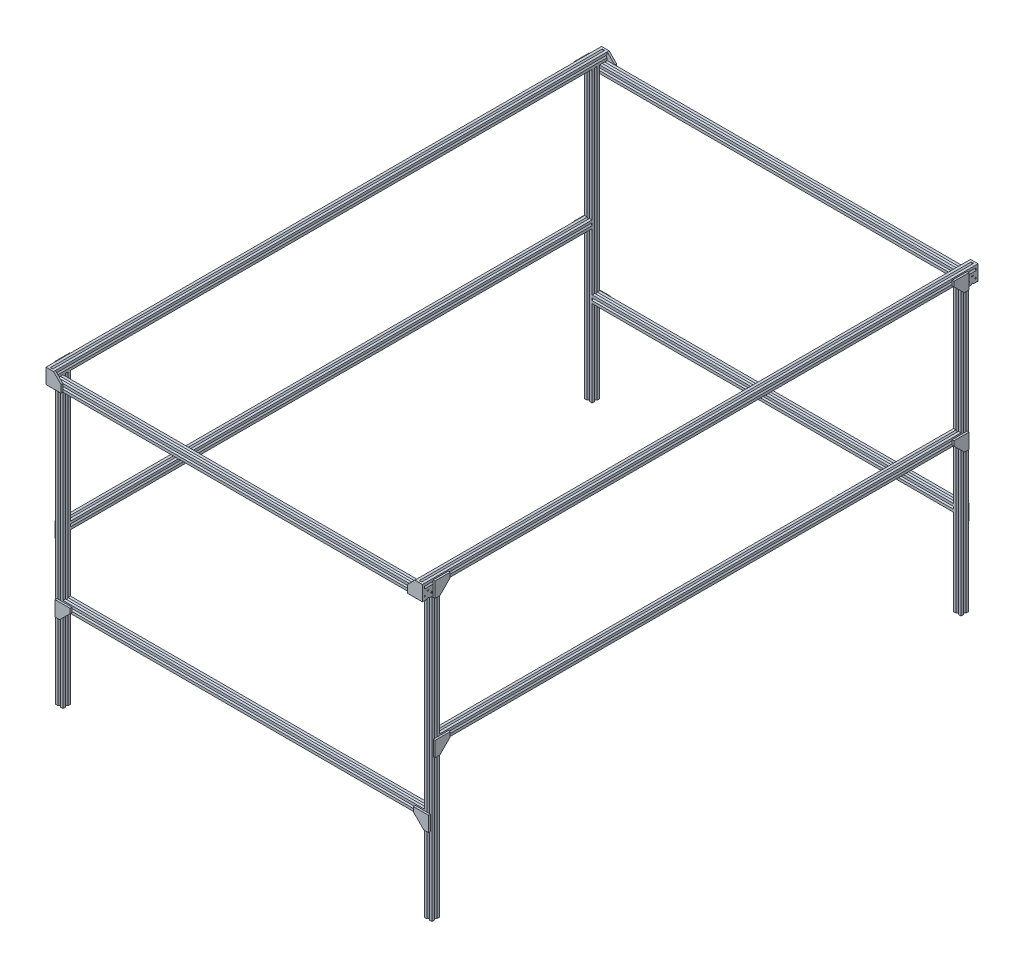
SolidWorks part; units mm, degrees
ref_plane "Front Plane" through (0, 0, 0) normal (0, 0, 1) x (1, 0, 0)
ref_plane "Top Plane" through (0, 0, 0) normal (0, 1, 0) x (1, 0, 0)
ref_plane "Right Plane" through (0, 0, 0) normal (1, 0, 0) x (0, 0, -1)
sketch "Sketch1" plane through (0, 0, 0) normal (0, 1, 0) x (1, 0, 0)
  line L48 (-13.2, 20) -> (-10, 16.8)
  line L49 (-10, 16.8) -> (-6.8, 20)
  line L50 (0, 13.2) -> (-3.2, 10)
  line L51 (-3.2, 10) -> (0, 6.8)
  line L100 (0, 0) -> (-28.059, 28.059) construction
  line L101 (-20, 0) -> (-13.2, 0)
  line L102 (-20, 0) -> (-20, 6.8)
  line L103 (-20, 20) -> (-13.2, 20)
  line L104 (0, 0) -> (0, 6.8)
  line L105 (-13.2, 20) -> (-13.2, 18.2)
  line L106 (0, 20) -> (-11.7678, 8.2322) construction
  line L107 (-7.05, 6.1) -> (-12.95, 6.1)
  line L108 (-6.1, 7.05) -> (-6.1, 12.95)
  line L109 (-7.05, 13.9) -> (-12.95, 13.9)
  line L110 (-13.9, 7.05) -> (-13.9, 12.95)
  line L111 (-6.1, 6.1) -> (-13.9, 13.9) construction
  line L112 (-6.1, 13.9) -> (-13.9, 6.1) construction
  line L113 (-15.45, 16.4) -> (-12.95, 13.9)
  line L114 (-6.8, 18.2) -> (-6.8, 20)
  line L115 (-18.2, 6.8) -> (-20, 6.8)
  line L116 (-20, 13.2) -> (-20, 20)
  line L117 (-20, 13.2) -> (-18.2, 13.2)
  line L118 (-10, 10) -> (-10, 13.9) construction
  line L119 (-3.6, 4.55) -> (-6.1, 7.05)
  line L120 (-15.45, 16.4) -> (-15.45, 18.2)
  line L121 (-15.45, 18.2) -> (-13.2, 18.2)
  line L122 (-6.8, 18.2) -> (-4.55, 18.2)
  line L123 (-4.55, 18.2) -> (-4.55, 16.4)
  line L124 (-4.55, 16.4) -> (-7.05, 13.9)
  line L125 (-3.6, 4.55) -> (-1.8, 4.55)
  line L126 (-1.8, 4.55) -> (-1.8, 6.8)
  line L127 (0, 6.8) -> (-1.8, 6.8)
  line L128 (-1.8, 13.2) -> (0, 13.2)
  line L129 (-1.8, 13.2) -> (-1.8, 15.45)
  line L130 (-1.8, 15.45) -> (-3.6, 15.45)
  line L131 (-3.6, 15.45) -> (-6.1, 12.95)
  line L132 (-18.2, 4.55) -> (-16.4, 4.55)
  line L133 (-16.4, 15.45) -> (-13.9, 12.95)
  line L134 (-16.4, 15.45) -> (-18.2, 15.45)
  line L135 (-18.2, 15.45) -> (-18.2, 13.2)
  line L136 (-20, 13.2) -> (-18.2, 13.2)
  line L137 (-18.2, 6.8) -> (-20, 6.8)
  line L138 (-16.4, 4.55) -> (-13.9, 7.05)
  line L139 (-18.2, 6.8) -> (-18.2, 4.55)
  line L140 (-4.55, 3.6) -> (-7.05, 6.1)
  line L141 (-15.45, 3.6) -> (-12.95, 6.1)
  line L142 (-15.45, 1.8) -> (-15.45, 3.6)
  line L143 (-13.2, 1.8) -> (-15.45, 1.8)
  line L144 (-13.2, 1.8) -> (-13.2, 0)
  line L145 (-4.55, 3.6) -> (-4.55, 1.8)
  line L146 (-4.55, 1.8) -> (-6.8, 1.8)
  line L147 (-6.8, 0) -> (-6.8, 1.8)
  line L148 (-6.8, 20) -> (0, 20)
  line L149 (0, 13.2) -> (0, 20)
  line L150 (-6.8, 0) -> (0, 0)
  line L151 (-13.9, 6.1) -> (-25.5045, -5.5045) construction
  line L152 (-6.8, 0) -> (-10, 3.2)
  line L153 (-10, 3.2) -> (-13.2, 0)
  line L154 (-20, 6.8) -> (-16.8, 10)
  line L155 (-16.8, 10) -> (-20, 13.2)
  circle A1 centre (-10, 10) radius 2.5
  point P140 (-10, 16.4)
  point P154 (-6.8, 19.1)
  point P161 (-19.1, 6.8)
  dimension "D13" = 5
  dimension "D12" = 20
  dimension "D14" = 7.8
  dimension "D15" = 7.8
  dimension "D16" = 6.8
  dimension "D17" = 6.8
  dimension "D18" = 1.8
  dimension "D19" = 10.9
  dimension "D20" = 1.8
  dimension "D21" = 10.9
  dimension "D22" = 20
extrude "Vertical Leg" add sketch "Sketch1" along normal blind 767.075 contours L147 L150 L104 L127 L126 L125 L119 L108 L131 L130 L129 L128 L149 L148 L114 L122 L123 L124 L109 L113 L120 L121 L105 L103 L116 L117 L135 L134 L133 L110 L138 L132 L139 L115 L102 L101 L144 L143 L142 L141 L107 L140 L145 L146 A1 | L124 L123 L122 L114 L49 L48 L105 L121 L120 L113 L109 | L155 L154 L115 L139 L132 L138 L110 L133 L134 L135 L117 | L130 L131 L108 L119 L125 L126 L127 L51 L50 L128 L129 | A1 | L153 L152 L147 L146 L145 L140 L107 L141 L142 L143 L144 region at (-13.4828, 0, -19.1) region at (-10, 0, -16.3803) region at (-16.3803, 0, -10) region at (-3.6197, 0, -10) region at (-10, 0, -3.6197) region at (-10, 0, -10)
sketch "Sketch2" plane through (-20, 0, 0) normal (-1, 0, 0) x (0, 0, 1)
  line L0 (0, 228.6) -> (-28.059, 256.659) construction
  line L1 (-20, 228.6) -> (-13.2, 228.6)
  line L2 (-20, 228.6) -> (-20, 235.4)
  line L3 (-20, 248.6) -> (-13.2, 248.6)
  line L4 (0, 228.6) -> (0, 235.4)
  line L5 (-13.2, 248.6) -> (-13.2, 246.8)
  line L6 (0, 248.6) -> (-11.7678, 236.8322) construction
  line L7 (-7.05, 234.7) -> (-12.95, 234.7)
  line L8 (-6.1, 235.65) -> (-6.1, 241.55)
  line L9 (-7.05, 242.5) -> (-12.95, 242.5)
  line L10 (-13.9, 235.65) -> (-13.9, 241.55)
  line L11 (-6.1, 234.7) -> (-13.9, 242.5) construction
  line L12 (-6.1, 242.5) -> (-13.9, 234.7) construction
  line L13 (-15.45, 245) -> (-12.95, 242.5)
  line L14 (-6.8, 246.8) -> (-6.8, 248.6)
  line L15 (-18.2, 235.4) -> (-20, 235.4)
  line L16 (-20, 241.8) -> (-20, 248.6)
  line L17 (-20, 241.8) -> (-18.2, 241.8)
  line L18 (-10, 238.6) -> (-10, 242.5) construction
  line L19 (-3.6, 233.15) -> (-6.1, 235.65)
  line L20 (-15.45, 245) -> (-15.45, 246.8)
  line L21 (-15.45, 246.8) -> (-13.2, 246.8)
  line L22 (-6.8, 246.8) -> (-4.55, 246.8)
  line L23 (-4.55, 246.8) -> (-4.55, 245)
  line L24 (-4.55, 245) -> (-7.05, 242.5)
  line L25 (-3.6, 233.15) -> (-1.8, 233.15)
  line L26 (-1.8, 233.15) -> (-1.8, 235.4)
  line L27 (0, 235.4) -> (-1.8, 235.4)
  line L28 (-1.8, 241.8) -> (0, 241.8)
  line L29 (-1.8, 241.8) -> (-1.8, 244.05)
  line L30 (-1.8, 244.05) -> (-3.6, 244.05)
  line L31 (-3.6, 244.05) -> (-6.1, 241.55)
  line L32 (-18.2, 233.15) -> (-16.4, 233.15)
  line L33 (-16.4, 244.05) -> (-13.9, 241.55)
  line L34 (-16.4, 244.05) -> (-18.2, 244.05)
  line L35 (-18.2, 244.05) -> (-18.2, 241.8)
  line L36 (-20, 241.8) -> (-18.2, 241.8)
  line L37 (-18.2, 235.4) -> (-20, 235.4)
  line L38 (-16.4, 233.15) -> (-13.9, 235.65)
  line L39 (-18.2, 235.4) -> (-18.2, 233.15)
  line L40 (-4.55, 232.2) -> (-7.05, 234.7)
  line L41 (-15.45, 232.2) -> (-12.95, 234.7)
  line L42 (-15.45, 230.4) -> (-15.45, 232.2)
  line L43 (-13.2, 230.4) -> (-15.45, 230.4)
  line L44 (-13.2, 230.4) -> (-13.2, 228.6)
  line L45 (-4.55, 232.2) -> (-4.55, 230.4)
  line L46 (-4.55, 230.4) -> (-6.8, 230.4)
  line L47 (-6.8, 228.6) -> (-6.8, 230.4)
  line L48 (-6.8, 248.6) -> (0, 248.6)
  line L49 (0, 241.8) -> (0, 248.6)
  line L50 (-6.8, 228.6) -> (0, 228.6)
  line L51 (-13.9, 234.7) -> (-25.5045, 223.0955) construction
  line L52 (-103.3225, 228.6) -> (77.3135, 228.6) construction
  line L53 (0, 0) -> (-6.8, 0) construction
  line L54 (20, 747.075) -> (-8.059, 775.134) construction
  line L55 (0, 747.075) -> (6.8, 747.075)
  line L56 (0, 747.075) -> (0, 753.875)
  line L57 (0, 767.075) -> (6.8, 767.075)
  line L58 (20, 747.075) -> (20, 753.875)
  line L59 (6.8, 767.075) -> (6.8, 765.275)
  line L60 (20, 767.075) -> (8.2322, 755.3072) construction
  line L61 (12.95, 753.175) -> (7.05, 753.175)
  line L62 (13.9, 754.125) -> (13.9, 760.025)
  line L63 (12.95, 760.975) -> (7.05, 760.975)
  line L64 (6.1, 754.125) -> (6.1, 760.025)
  line L65 (13.9, 753.175) -> (6.1, 760.975) construction
  line L66 (13.9, 760.975) -> (6.1, 753.175) construction
  line L67 (4.55, 763.475) -> (7.05, 760.975)
  line L68 (13.2, 765.275) -> (13.2, 767.075)
  line L69 (1.8, 753.875) -> (0, 753.875)
  line L70 (0, 760.275) -> (0, 767.075)
  line L71 (0, 760.275) -> (1.8, 760.275)
  line L72 (10, 757.075) -> (10, 760.975) construction
  line L73 (16.4, 751.625) -> (13.9, 754.125)
  line L74 (4.55, 763.475) -> (4.55, 765.275)
  line L75 (4.55, 765.275) -> (6.8, 765.275)
  line L76 (13.2, 765.275) -> (15.45, 765.275)
  line L77 (15.45, 765.275) -> (15.45, 763.475)
  line L78 (15.45, 763.475) -> (12.95, 760.975)
  line L79 (16.4, 751.625) -> (18.2, 751.625)
  line L80 (18.2, 751.625) -> (18.2, 753.875)
  line L81 (20, 753.875) -> (18.2, 753.875)
  line L82 (18.2, 760.275) -> (20, 760.275)
  line L83 (18.2, 760.275) -> (18.2, 762.525)
  line L84 (18.2, 762.525) -> (16.4, 762.525)
  line L85 (16.4, 762.525) -> (13.9, 760.025)
  line L86 (1.8, 751.625) -> (3.6, 751.625)
  line L87 (3.6, 762.525) -> (6.1, 760.025)
  line L88 (3.6, 762.525) -> (1.8, 762.525)
  line L89 (1.8, 762.525) -> (1.8, 760.275)
  line L90 (0, 760.275) -> (1.8, 760.275)
  line L91 (1.8, 753.875) -> (0, 753.875)
  line L92 (3.6, 751.625) -> (6.1, 754.125)
  line L93 (1.8, 753.875) -> (1.8, 751.625)
  line L94 (15.45, 750.675) -> (12.95, 753.175)
  line L95 (4.55, 750.675) -> (7.05, 753.175)
  line L96 (4.55, 748.875) -> (4.55, 750.675)
  line L97 (6.8, 748.875) -> (4.55, 748.875)
  line L98 (6.8, 748.875) -> (6.8, 747.075)
  line L99 (15.45, 750.675) -> (15.45, 748.875)
  line L100 (15.45, 748.875) -> (13.2, 748.875)
  line L101 (13.2, 747.075) -> (13.2, 748.875)
  line L102 (13.2, 767.075) -> (20, 767.075)
  line L103 (20, 760.275) -> (20, 767.075)
  line L104 (13.2, 747.075) -> (20, 747.075)
  line L105 (6.1, 753.175) -> (-5.5045, 741.5705) construction
  line L106 (-13.2, 248.6) -> (-10, 245.4)
  line L107 (-10, 767.075) -> (-10, 0) construction
  line L108 (-10, 245.4) -> (-6.8, 248.6)
  line L109 (0, 241.8) -> (-3.2, 238.6)
  line L110 (-3.2, 238.6) -> (0, 235.4)
  line L111 (-6.8, 228.6) -> (-10, 231.8)
  line L112 (-10, 231.8) -> (-13.2, 228.6)
  line L113 (-20, 235.4) -> (-16.8, 238.6)
  line L114 (-16.8, 238.6) -> (-20, 241.8)
  line L115 (6.8, 767.075) -> (10, 763.875)
  line L116 (10, 763.875) -> (13.2, 767.075)
  line L117 (20, 760.275) -> (16.8, 757.075)
  line L118 (16.8, 757.075) -> (20, 753.875)
  line L119 (13.2, 747.075) -> (10, 750.275)
  line L120 (10, 750.275) -> (6.8, 747.075)
  line L121 (0, 753.875) -> (3.2, 757.075)
  line L122 (3.2, 757.075) -> (0, 760.275)
  circle A0 centre (-10, 238.6) radius 2.5
  circle A1 centre (10, 757.075) radius 2.5
  point P23 (-10, 245)
  point P44 (-19.1, 235.4)
  point P84 (10, 763.475)
  point P98 (13.2, 766.175)
  point P105 (0.9, 753.875)
  line M5 (-20, 767.075) -> (-20, 0)
  line M114 (-13.2, 0) -> (-13.2, 767.075)
  dimension "D2" = 5
  dimension "D14" = 5
  dimension "D1" = 20
  dimension "D3" = 7.8
  dimension "D4" = 7.8
  dimension "D5" = 6.8
  dimension "D6" = 6.8
  dimension "D7" = 1.8
  dimension "D8" = 10.9
  dimension "D9" = 1.8
  dimension "D10" = 10.9
  dimension "D11" = 20
  dimension "D12" = 228.6
  dimension "D13" = 20
  dimension "D15" = 7.8
  dimension "D16" = 7.8
  dimension "D17" = 6.8
  dimension "D18" = 6.8
  dimension "D19" = 1.8
  dimension "D20" = 10.9
  dimension "D21" = 1.8
  dimension "D22" = 10.9
  dimension "D23" = 20
extrude "Short Horizontal" add sketch "Sketch2" along normal blind 479.425 contours L47 L50 L4 L27 L26 L25 L19 L8 L31 L30 L29 L28 L49 L48 L14 L22 L23 L24 L9 L13 L41 L7 L40 L45 L46 A0 | L43 L42 L41 L13 L20 L21 L3 L17 L35 L34 L33 L10 L38 L32 L39 L15 L1 M5 | L101 L104 L58 L81 L80 L79 L73 L62 L85 L84 L83 L82 L103 L102 L68 L76 L77 L78 L63 L67 L74 L75 L59 L57 L70 L71 L89 L88 L87 L64 L92 L86 L93 L69 L56 L55 L98 L97 L96 L95 L61 L94 L99 L100 A1 | L116 L115 L59 L75 L74 L67 L63 L78 L77 L76 L68 | L122 L121 L69 L93 L86 L92 L64 L87 L88 L89 L71 | L118 L117 L82 L83 L84 L85 L62 L73 L79 L80 L81 | L120 L119 L101 L100 L99 L94 L61 L95 L96 L97 L98 | A1 | L108 L106 L13 L9 L24 L23 L22 L14 M114 | A0 | L114 L113 L15 L39 L32 L38 L10 L33 L34 L35 L17 | L21 L20 L13 M114 | L110 L109 L28 L29 L30 L31 L8 L19 L25 L26 L27 | L112 L111 L47 L46 L45 L40 L7 L41 M114 | L43 L41 L42 M114 region at (-20, 232, -19.7888) region at (-20, 232.2728, -9.221) region at (-20, 238.6, -16.3803) region at (-20, 231.9346, -14.1808) region at (-20, 238.6, -12.9604) region at (-20, 244.9272, -9.221) region at (-20, 245.2654, -14.1808) region at (-20, 238.6, -3.6197) region at (-20, 750.475, 0.2828) region at (-20, 750.6947, 10) region at (-20, 757.075, 3.6197) region at (-20, 757.075, 16.3803) region at (-20, 763.4553, 10) region at (-20, 238.6, -10) region at (-20, 757.075, 10)
sketch "Sketch3" plane through (0, 0, -20) normal (0, 0, -1) x (-1, 0, 0)
  line L0 (-37.0014, 401) -> (61.5382, 401) construction
  line L1 (499.425, 248.6) -> (20, 248.6) construction
  line L2 (-37.0014, 421) -> (61.5382, 421) construction
  line L3 (-37.0014, 767.075) -> (61.5382, 767.075) construction
  line L4 (20, 401) -> (-8.059, 429.059) construction
  line L5 (0, 401) -> (6.8, 401)
  line L6 (0, 401) -> (0, 407.8)
  line L7 (0, 421) -> (6.8, 421)
  line L8 (20, 401) -> (20, 407.8)
  line L9 (6.8, 421) -> (6.8, 419.2)
  line L10 (20, 421) -> (8.2322, 409.2322) construction
  line L11 (12.95, 407.1) -> (7.05, 407.1)
  line L12 (13.9, 408.05) -> (13.9, 413.95)
  line L13 (12.95, 414.9) -> (7.05, 414.9)
  line L14 (6.1, 408.05) -> (6.1, 413.95)
  line L15 (13.9, 407.1) -> (6.1, 414.9) construction
  line L16 (13.9, 414.9) -> (6.1, 407.1) construction
  line L17 (4.55, 417.4) -> (7.05, 414.9)
  line L18 (13.2, 419.2) -> (13.2, 421)
  line L19 (1.8, 407.8) -> (0, 407.8)
  line L20 (0, 414.2) -> (0, 421)
  line L21 (0, 414.2) -> (1.8, 414.2)
  line L22 (10, 411) -> (10, 414.9) construction
  line L23 (16.4, 405.55) -> (13.9, 408.05)
  line L24 (4.55, 417.4) -> (4.55, 419.2)
  line L25 (4.55, 419.2) -> (6.8, 419.2)
  line L26 (13.2, 419.2) -> (15.45, 419.2)
  line L27 (15.45, 419.2) -> (15.45, 417.4)
  line L28 (15.45, 417.4) -> (12.95, 414.9)
  line L29 (16.4, 405.55) -> (18.2, 405.55)
  line L30 (18.2, 405.55) -> (18.2, 407.8)
  line L31 (20, 407.8) -> (18.2, 407.8)
  line L32 (18.2, 414.2) -> (20, 414.2)
  line L33 (18.2, 414.2) -> (18.2, 416.45)
  line L34 (18.2, 416.45) -> (16.4, 416.45)
  line L35 (16.4, 416.45) -> (13.9, 413.95)
  line L36 (1.8, 405.55) -> (3.6, 405.55)
  line L37 (3.6, 416.45) -> (6.1, 413.95)
  line L38 (3.6, 416.45) -> (1.8, 416.45)
  line L39 (1.8, 416.45) -> (1.8, 414.2)
  line L40 (0, 414.2) -> (1.8, 414.2)
  line L41 (1.8, 407.8) -> (0, 407.8)
  line L42 (3.6, 405.55) -> (6.1, 408.05)
  line L43 (1.8, 407.8) -> (1.8, 405.55)
  line L44 (15.45, 404.6) -> (12.95, 407.1)
  line L45 (4.55, 404.6) -> (7.05, 407.1)
  line L46 (4.55, 402.8) -> (4.55, 404.6)
  line L47 (6.8, 402.8) -> (4.55, 402.8)
  line L48 (6.8, 402.8) -> (6.8, 401)
  line L49 (15.45, 404.6) -> (15.45, 402.8)
  line L50 (15.45, 402.8) -> (13.2, 402.8)
  line L51 (13.2, 401) -> (13.2, 402.8)
  line L52 (13.2, 421) -> (20, 421)
  line L53 (20, 414.2) -> (20, 421)
  line L54 (13.2, 401) -> (20, 401)
  line L55 (6.1, 407.1) -> (-5.5045, 395.4955) construction
  line L56 (20, 767.075) -> (-8.059, 795.134) construction
  line L57 (0, 767.075) -> (6.8, 767.075)
  line L58 (0, 767.075) -> (0, 773.875)
  line L59 (0, 787.075) -> (6.8, 787.075)
  line L60 (20, 767.075) -> (20, 773.875)
  line L61 (6.8, 787.075) -> (6.8, 785.275)
  line L62 (20, 787.075) -> (8.2322, 775.3072) construction
  line L63 (12.95, 773.175) -> (7.05, 773.175)
  line L64 (13.9, 774.125) -> (13.9, 780.025)
  line L65 (12.95, 780.975) -> (7.05, 780.975)
  line L66 (6.1, 774.125) -> (6.1, 780.025)
  line L67 (13.9, 773.175) -> (6.1, 780.975) construction
  line L68 (13.9, 780.975) -> (6.1, 773.175) construction
  line L69 (4.55, 783.475) -> (7.05, 780.975)
  line L70 (13.2, 785.275) -> (13.2, 787.075)
  line L71 (1.8, 773.875) -> (0, 773.875)
  line L72 (0, 780.275) -> (0, 787.075)
  line L73 (0, 780.275) -> (1.8, 780.275)
  line L74 (10, 777.075) -> (10, 780.975) construction
  line L75 (16.4, 771.625) -> (13.9, 774.125)
  line L76 (4.55, 783.475) -> (4.55, 785.275)
  line L77 (4.55, 785.275) -> (6.8, 785.275)
  line L78 (13.2, 785.275) -> (15.45, 785.275)
  line L79 (15.45, 785.275) -> (15.45, 783.475)
  line L80 (15.45, 783.475) -> (12.95, 780.975)
  line L81 (16.4, 771.625) -> (18.2, 771.625)
  line L82 (18.2, 771.625) -> (18.2, 773.875)
  line L83 (20, 773.875) -> (18.2, 773.875)
  line L84 (18.2, 780.275) -> (20, 780.275)
  line L85 (18.2, 780.275) -> (18.2, 782.525)
  line L86 (18.2, 782.525) -> (16.4, 782.525)
  line L87 (16.4, 782.525) -> (13.9, 780.025)
  line L88 (1.8, 771.625) -> (3.6, 771.625)
  line L89 (3.6, 782.525) -> (6.1, 780.025)
  line L90 (3.6, 782.525) -> (1.8, 782.525)
  line L91 (1.8, 782.525) -> (1.8, 780.275)
  line L92 (0, 780.275) -> (1.8, 780.275)
  line L93 (1.8, 773.875) -> (0, 773.875)
  line L94 (3.6, 771.625) -> (6.1, 774.125)
  line L95 (1.8, 773.875) -> (1.8, 771.625)
  line L96 (15.45, 770.675) -> (12.95, 773.175)
  line L97 (4.55, 770.675) -> (7.05, 773.175)
  line L98 (4.55, 768.875) -> (4.55, 770.675)
  line L99 (6.8, 768.875) -> (4.55, 768.875)
  line L100 (6.8, 768.875) -> (6.8, 767.075)
  line L101 (15.45, 770.675) -> (15.45, 768.875)
  line L102 (15.45, 768.875) -> (13.2, 768.875)
  line L103 (13.2, 767.075) -> (13.2, 768.875)
  line L104 (13.2, 787.075) -> (20, 787.075)
  line L105 (20, 780.275) -> (20, 787.075)
  line L106 (13.2, 767.075) -> (20, 767.075)
  line L107 (6.1, 773.175) -> (-5.5045, 761.5705) construction
  line L108 (6.8, 0) -> (0, 0) construction
  line L109 (6.8, 787.075) -> (10, 783.875)
  line L110 (10, 783.875) -> (13.2, 787.075)
  line L111 (20, 780.275) -> (16.8, 777.075)
  line L112 (16.8, 777.075) -> (20, 773.875)
  line L113 (0, 780.275) -> (3.2, 777.075)
  line L114 (3.2, 777.075) -> (0, 773.875)
  line L115 (6.8, 767.075) -> (10, 770.275)
  line L116 (10, 770.275) -> (13.2, 767.075)
  line L117 (6.8, 421) -> (10, 417.8)
  line L118 (10, 767.075) -> (10, 0) construction
  line L119 (10, 417.8) -> (13.2, 421)
  line L120 (20, 414.2) -> (16.8, 411)
  line L121 (16.8, 411) -> (20, 407.8)
  line L122 (6.8, 401) -> (10, 404.2)
  line L123 (10, 404.2) -> (13.2, 401)
  line L124 (0, 407.8) -> (3.2, 411)
  line L125 (3.2, 411) -> (0, 414.2)
  circle A0 centre (10, 411) radius 2.5
  circle A1 centre (10, 777.075) radius 2.5
  point P31 (10, 417.4)
  point P52 (0.9, 407.8)
  point P88 (10, 783.475)
  point P102 (13.2, 786.175)
  point P109 (0.9, 773.875)
  line M13 (20, 248.6) -> (20, 767.075)
  line M14 (20, 767.075) -> (13.2, 767.075)
  line M131 (13.2, 767.075) -> (13.2, 0)
  dimension "D5" = 5
  dimension "D16" = 5
  dimension "D1" = 152.4
  dimension "D2" = 20
  dimension "D3" = 346.075
  dimension "D4" = 20
  dimension "D6" = 7.8
  dimension "D7" = 7.8
  dimension "D8" = 6.8
  dimension "D9" = 6.8
  dimension "D10" = 1.8
  dimension "D11" = 10.9
  dimension "D12" = 1.8
  dimension "D13" = 10.9
  dimension "D14" = 20
  dimension "D15" = 20
  dimension "D17" = 7.8
  dimension "D18" = 7.8
  dimension "D19" = 6.8
  dimension "D20" = 6.8
  dimension "D21" = 1.8
  dimension "D22" = 10.9
  dimension "D23" = 1.8
  dimension "D24" = 10.9
  dimension "D25" = 20
  dimension "D26" = 401
extrude "Long Horizontal" add sketch "Sketch3" along normal blind 692.15 contours L48 L47 L46 L45 L11 L44 L28 L13 L17 L24 L25 L9 L7 L20 L21 L39 L38 L37 L14 L42 L36 L43 L19 L6 L5 A0 | L54 L31 L30 L29 L23 L12 L35 L34 L33 L32 L52 L26 L27 L28 L44 L49 L50 M13 | L106 L83 L82 L81 L75 L64 L87 L86 L85 L84 L78 L79 L80 L96 L101 L102 M13 M14 | L105 L104 L70 M14 | L100 L99 L98 L97 L63 L96 L80 L65 L69 L76 L77 L61 L59 L72 L73 L91 L90 L89 L66 L94 L88 L95 L71 L58 L57 A1 | L119 L117 L9 L25 L24 L17 L13 L28 M131 | L28 L27 L26 M131 | L121 L120 L32 L33 L34 L35 L12 L23 L29 L30 L31 | L122 L123 L44 L11 L45 L46 L47 L48 M131 | L50 L49 L44 M131 | A0 | L125 L124 L19 L43 L36 L42 L14 L37 L38 L39 L21 | L110 L109 L61 L77 L76 L69 L65 L80 L79 L78 L70 | L113 L114 L71 L95 L88 L94 L66 L89 L90 L91 L73 | L112 L111 L84 L85 L86 L87 L64 L75 L81 L82 L83 | A1 | L115 L116 L103 L102 L101 L96 L63 L97 L98 L99 L100 region at (-0.2396, 404.4, -20) region at (-9.221, 404.6728, -20) region at (-3.6197, 411, -20) region at (-13.4112, 401.9, -20) region at (-14.1808, 404.3346, -20) region at (-16.3803, 411, -20) region at (-9.221, 417.3272, -20) region at (-14.1808, 417.6654, -20) region at (-16.6, 767.3578, -20) region at (-10, 770.6947, -20) region at (-16.3803, 777.075, -20) region at (-3.6197, 777.075, -20) region at (-10, 783.4553, -20) region at (-10, 411, -20) region at (-10, 777.075, -20)
extrude "Long Horizontal Backwards" add sketch "Sketch3<3>" against normal blind 40 contours L84 L105 L104 L70 L78 L79 L80 L65 L69 L76 L77 L61 L59 L72 L73 L91 L90 L89 L66 L94 L88 L95 L71 L58 L57 L100 L99 L98 L97 L63 L96 L101 L102 L103 L60 L83 L82 L81 L75 L64 L87 L86 L85 A1 M14 | L113 L114 L71 L95 L88 L94 L66 L89 L90 L91 L73 | L110 L109 L61 L77 L76 L69 L65 L80 L79 L78 L70 | L112 L111 L84 L85 L86 L87 L64 L75 L81 L82 L83 | L115 L116 L103 L102 L101 L96 L63 L97 L98 L99 L100 | A1 region at (-0.2828, 770.475, -20) region at (-10, 770.6947, -20) region at (-3.6197, 777.075, -20) region at (-16.3803, 777.075, -20) region at (-10, 783.4553, -20) region at (-10, 777.075, -20)
sketch "Sketch3<3>" plane through (0, 0, -20) normal (0, 0, -1) x (-1, 0, 0) same geometry as "Sketch3"
extrude "Short Horizontal Backwards" add sketch "Sketch2<3>" against normal blind 20 contours L101 L104 L58 L81 L80 L79 L73 L62 L85 L84 L83 L82 L103 L102 L68 L76 L77 L78 L63 L67 L74 L75 L59 L57 L70 L71 L89 L88 L87 L64 L92 L86 L93 L69 L56 L55 L98 L97 L96 L95 L61 L94 L99 L100 A1 | L116 L115 L59 L75 L74 L67 L63 L78 L77 L76 L68 | L122 L121 L69 L93 L86 L92 L64 L87 L88 L89 L71 | A1 | L118 L117 L82 L83 L84 L85 L62 L73 L79 L80 L81 | L120 L119 L101 L100 L99 L94 L61 L95 L96 L97 L98 region at (-20, 750.475, 0.2828) region at (-20, 750.6947, 10) region at (-20, 757.075, 3.6197) region at (-20, 757.075, 16.3803) region at (-20, 763.4553, 10) region at (-20, 757.075, 10)
sketch "Sketch2<3>" plane through (-20, 0, 0) normal (-1, 0, 0) x (0, 0, 1) same geometry as "Sketch2"
sketch "Sketch4" plane through (0, 0, 0) normal (1, 0, 0) x (0, 0, -1)
  line L0 (3.5094, 743.5656) -> (16.4906, 743.5656)
  line L1 (16.4906, 743.5656) -> (43.5094, 770.5844)
  line L2 (43.5094, 770.5844) -> (43.5094, 783.5656)
  line L3 (43.5094, 783.5656) -> (3.5094, 783.5656)
  line L4 (3.5094, 783.5656) -> (3.5094, 743.5656)
  line L7 (3.8545, 417.1455) -> (43.8545, 417.1455)
  line L8 (43.8545, 417.1455) -> (43.8545, 404.8545)
  line L9 (43.8545, 404.8545) -> (16.1455, 377.1455)
  line L10 (16.1455, 377.1455) -> (3.8545, 377.1455)
  line L11 (3.8545, 377.1455) -> (3.8545, 417.1455)
  line L14 (10, 767.075) -> (10, 0) construction
  line L15 (712.15, 411) -> (20, 411) construction
  point P2 (43.8545, 411)
  point P7 (10, 743.5656)
  point P9 (43.5094, 777.075)
  point P12 (10, 377.1455)
  dimension "D1" = 135
  dimension "D2" = 40
  dimension "D3" = 40
  dimension "D4" = 135
extrude "Brackets 1 & 2" add sketch "Sketch4" along normal blind 5
sketch "Sketch5" plane through (0, 0, 20) normal (0, 0, 1) x (1, 0, 0)
  line L0 (-40, 747.075) -> (-40, 767.075)
  line L1 (-40, 767.075) -> (-20, 787.075)
  line L2 (-20, 787.075) -> (0, 787.075)
  line L3 (0, 787.075) -> (0, 747.075)
  line L4 (0, 747.075) -> (-40, 747.075)
  dimension "D1" = 135
extrude "Bracket 3" add sketch "Sketch5" along normal blind 5
sketch "Sketch6" plane through (0, 0, 0) normal (0, 0, 1) x (1, 0, 0)
  line L0 (-43.6796, 244.9204) -> (-43.6796, 232.2796)
  line L1 (-43.6796, 232.2796) -> (-16.3204, 204.9204)
  line L2 (-16.3204, 204.9204) -> (-3.6796, 204.9204)
  line L3 (-3.6796, 204.9204) -> (-3.6796, 244.9204)
  line L4 (-3.6796, 244.9204) -> (-43.6796, 244.9204)
  line L7 (-499.425, 238.6) -> (-20, 238.6) construction
  line L8 (-10, 767.075) -> (-10, 0) construction
  point P5 (-10, 204.9204)
  point P7 (-43.6796, 238.6)
  dimension "D1" = 135
  dimension "D2" = 40
extrude "Bracket 4" add sketch "Sketch6" along normal blind 5
mirror "Mirror1" about plane through (0, 0, -712.15) normal (0, 0, -1) of bodies 114 103
mirror "Mirror2" about plane through (-499.425, 0, 0) normal (-1, 0, 0) of bodies 104
